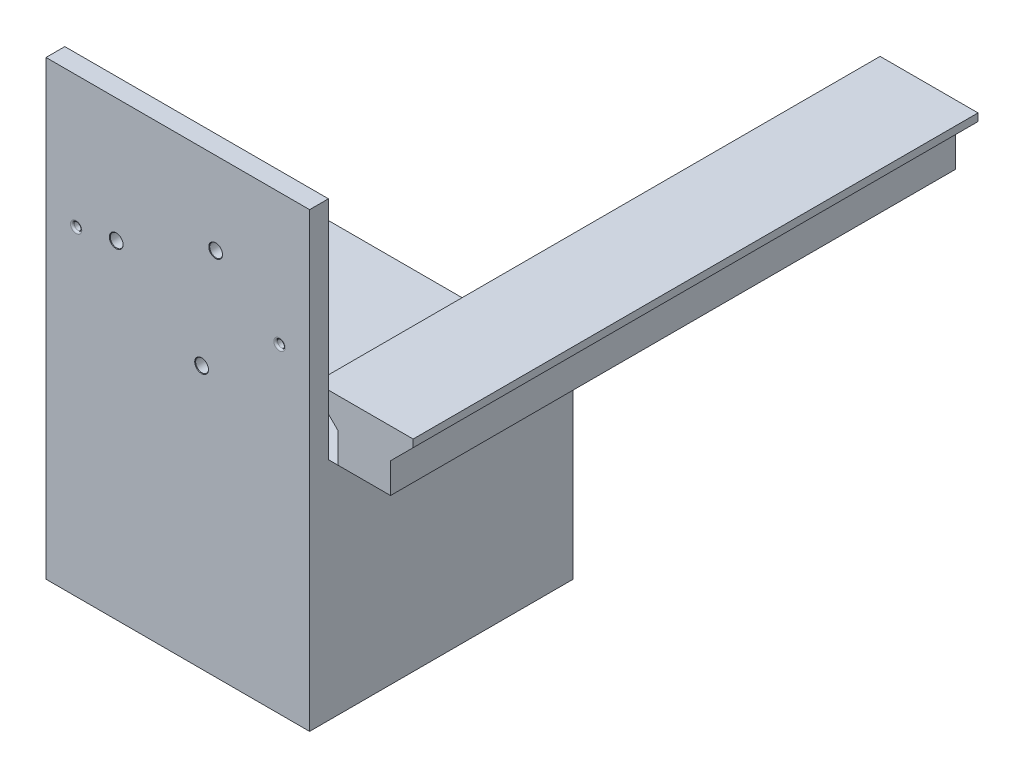
SolidWorks part; units mm, degrees
ref_plane "Front Plane" through (0, 0, 0) normal (0, 0, 1) x (1, 0, 0)
ref_plane "Top Plane" through (0, 0, 0) normal (0, 1, 0) x (1, 0, 0)
ref_plane "Right Plane" through (0, 0, 0) normal (1, 0, 0) x (0, 0, -1)
sketch "Sketch1" plane through (0, 0, 0) normal (0, 0, 1) x (1, 0, 0)
  line L1 (-35, -35) -> (35, -35)
  line L2 (-35, -35) -> (-35, 35)
  line L3 (-35, 35) -> (35, 35)
  line L4 (35, -35) -> (35, 35)
  line L5 (-35, -35) -> (35, 35) construction
  line L6 (-35, 35) -> (35, -35) construction
  point P0 (0, 0)
  dimension "D2" = 70
  dimension "D1" = 70
extrude "Boss-Extrude1" add sketch "Sketch1" along normal blind 5
sketch "Sketch2" plane through (0, 0, 5) normal (0, 0, 1) x (1, 0, 0)
  line L0 (0, 26.65) -> (0, -26.65) construction
  line L5 (-35, 35) -> (35, -35) construction
  line L6 (35, 35) -> (-35, -35) construction
  line L7 (-26.65, 0) -> (26.65, 0) construction
  line L8 (-16.3588, 2.1537) -> (0, 0) construction
  line L9 (10.0446, 13.0903) -> (0, 0) construction
  line L10 (0, 0) -> (6.3143, -15.244) construction
  line L11 (-27, 0) -> (0, 0) construction
  line L12 (0, 0) -> (27, 0) construction
  circle A0 centre (0, 0) radius 26.65 construction
  circle A1 centre (0, 0) radius 16.5 construction
  circle A2 centre (-27, 0) radius 1
  circle A3 centre (27, 0) radius 1
  point P8 (10.0446, 13.0903)
  point P9 (6.3143, -15.244)
  point P10 (-16.3588, 2.1537)
  dimension "D2" = 53.3
  dimension "D3" = 33
  dimension "D6" = 2
  dimension "D1" = 22.5
  dimension "D4" = 120
  dimension "D5" = 120
  dimension "D7" = 27
sketch "Sketch5" plane through (0, 0, 5) normal (0, 0, 1) x (1, 0, 0)
  point P0 (6.3143, -15.244)
  point P3 (10.0446, 13.0903)
  point P6 (-16.3588, 2.1537)
hole_wizard "M3 Clearance Hole1" positions "Sketch5" profile "Sketch4" hole size "M3" standard "ANSI Metric" end condition up to next
sketch "Sketch4" plane through (6.3143, -15.244, 5) normal (1, 0, 0) x (0, -1, 0)
  line L0 (0, 0) -> (0, 5)
  line L1 (0, 5) -> (1.7, 5)
  line L2 (1.7, 5) -> (1.7, 0.125)
  line L3 (1.7, 0.125) -> (1.825, 0)
  line L5 (1.825, 0) -> (0, 0)
  line L6 (-1.7, 0.125) -> (-1.825, 0) construction
  line L11 (0, -6.35) -> (0, 107.95) construction
  dimension "Thru Hole Dia." = 3.4
  dimension "Thru Hole Depth" = 5
  dimension "Near C'Sink Dia." = 3.65
  dimension "Near C'Sink Angle" = 90
extrude "Cut-Extrude1" cut sketch "Sketch2" against normal through all
fillet "Fillet1" radius 0.5 4 edges at (28, 0, 5) (28, 0, 0) (-26, 0, 5) (-26, 0, 0)
sketch "Sketch7" plane through (0, -35, 0) normal (0, 1, 0) x (1, 0, 0)
  line L0 (0, 10) -> (27, 10) construction
  line L1 (19.5, 160) -> (49.5, 160)
  line L2 (19.5, 160) -> (19.5, 10)
  line L3 (19.5, 10) -> (49.5, 10)
  line L4 (49.5, 160) -> (49.5, 10)
  line L7 (35, 0) -> (-35, 0) construction
  line L11 (27, 10) -> (34.5, 10) construction
  point P5 (34.5, 10)
  point P7 (0, 0)
  point P8 (0, 0)
  dimension "D1" = 27
  dimension "D2" = 30
  dimension "D3" = 150
  dimension "D4" = 10
  dimension "D5" = 7.5
extrude "Boss-Extrude5" add sketch "Sketch7" along normal blind 16
sketch "Sketch12" plane through (0, 0, -160) normal (0, 0, -1) x (-1, 0, 0)
  line L0 (-49.5, -35) -> (-41.5, -35)
  line L1 (-41.5, -35) -> (-41.5, -27)
  line L2 (-41.5, -27) -> (-47.5, -21)
  line L3 (-47.5, -21) -> (-47.5, -19)
  line L4 (-49.5, -19) -> (-19.5, -19) construction
  line L5 (-47.5, -19) -> (-49.5, -19)
  line L6 (-49.5, -19) -> (-49.5, -35)
  line L7 (-27.5, -35) -> (-27.5, -27)
  line L8 (-49.5, -35) -> (-19.5, -35) construction
  line L9 (-27.5, -27) -> (-21.5, -21)
  line L10 (-21.5, -21) -> (-21.5, -19)
  line L11 (-21.5, -19) -> (-19.5, -19)
  line L12 (-19.5, -19) -> (-19.5, -35)
  line L13 (-19.5, -35) -> (-27.5, -35)
  point P3 (0, 0)
  dimension "D1" = 8
  dimension "D2" = 6
  dimension "D3" = 8
  dimension "D4" = 2
sketch "Sketch13" plane through (0, -35, 0) normal (0, -1, 0) x (1, 0, 0)
  line L1 (-35, 5) -> (35, 5)
  line L2 (-35, 5) -> (-35, -65)
  line L3 (-35, -65) -> (35, -65)
  line L4 (35, 5) -> (35, -65)
  point P5 (40.4523, 5)
extrude "Boss-Extrude6" add sketch "Sketch13" along normal blind 50
extrude "Cut-Extrude2" cut sketch "Sketch12" against normal up to surface (150 mm away) up to face at (34.5, -27, -10)
chamfer "Chamfer1" distance 10 angle 45 1 edges at (0, -35, 0)
